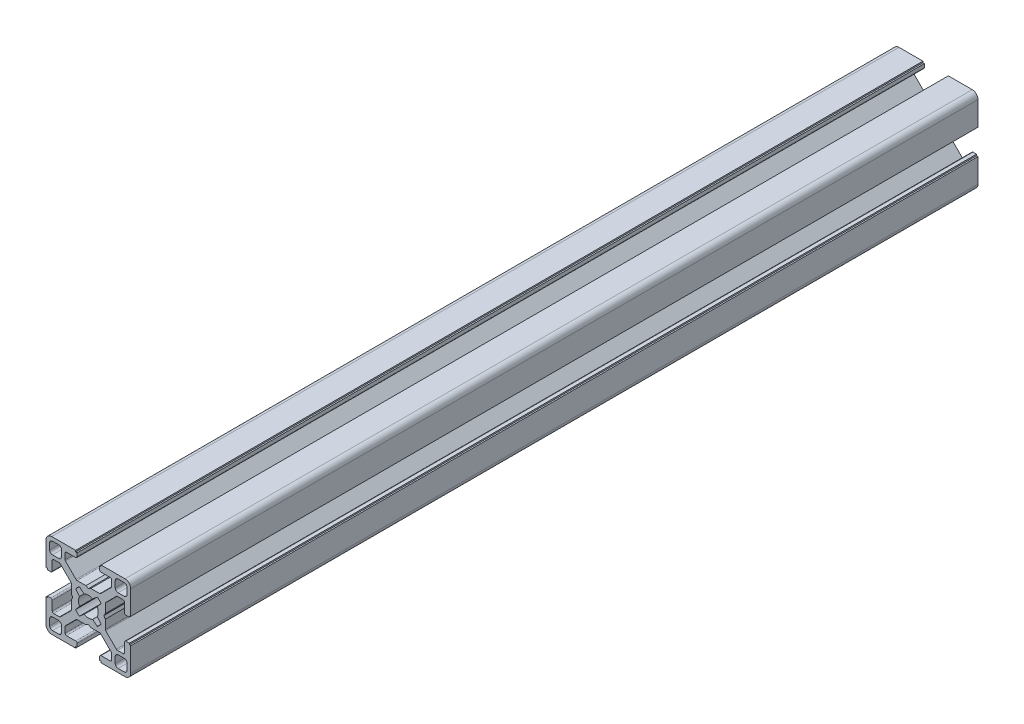
SolidWorks part; units mm, degrees
ref_plane "Front Plane" through (0, 0, 0) normal (0, 0, 1) x (1, 0, 0)
ref_plane "Top Plane" through (0, 0, 0) normal (0, 1, 0) x (1, 0, 0)
ref_plane "Right Plane" through (0, 0, 0) normal (1, 0, 0) x (0, 0, -1)
sketch "Sketch1" plane through (0, 0, 0) normal (0, 0, 1) x (1, 0, 0)
  line L0 (-15, 0) -> (15, 0) construction
  line L1 (0, -15) -> (0, 15) construction
  line L2 (-4.5, 15) -> (4.5, 15) construction
  line L3 (-4, -15) -> (4, -15) construction
  line L4 (-4.5, 15) -> (-4.5, 14.5)
  line L5 (-4.5, 14.5) -> (-4, 14.5)
  line L6 (-4, 14.5) -> (-4, 13.29)
  line L7 (-4.5, 12.79) -> (-7.7675, 12.79)
  line L8 (-8.2675, 12.29) -> (-8.2675, 10.2707)
  line L9 (-8.1211, 9.9171) -> (-4.3504, 6.1464)
  line L10 (-3.9968, 6) -> (0, 6)
  line L11 (0, 0) -> (-15, 15) construction
  line L12 (-4.5, 15) -> (-12.968, 15)
  line L14 (-12.705, 9.5135) -> (-10.5135, 9.5135)
  line L15 (-13.705, 10.5135) -> (-13.705, 12.705)
  line L16 (-12.705, 13.705) -> (-10.5135, 13.705)
  line L17 (-9.5135, 10.5135) -> (-9.5135, 12.705)
  line L18 (-13.705, 9.5135) -> (-9.5135, 13.705) construction
  line L19 (-13.705, 13.705) -> (-9.5135, 9.5135) construction
  line L20 (-3.1568, 4.5038) -> (-1.5303, 3.1477) construction
  line L21 (-4.5038, 3.1568) -> (-3.1477, 1.5303) construction
  line L22 (-6, 3.9968) -> (-6, 0)
  line L23 (-9.9171, 8.1211) -> (-6.1464, 4.3504)
  line L24 (-15, 4.5) -> (-15, 12.968)
  line L25 (-12.29, 8.2675) -> (-10.2707, 8.2675)
  line L26 (-12.79, 4.5) -> (-12.79, 7.7675)
  line L27 (-14.5, 4) -> (-13.29, 4)
  line L28 (-14.5, 4.5) -> (-14.5, 4)
  line L29 (-15, 4.5) -> (-14.5, 4.5)
  circle A0 centre (0, 0) radius 3.5
  arc A1 (-12.968, 15) -> (-15, 12.968) centre (-12.968, 12.968) ccw
  circle A2 centre (0, 0) radius 5.5 construction
  arc A3 (-10.5135, 9.5135) -> (-9.5135, 10.5135) centre (-10.5135, 10.5135) ccw
  arc A4 (-13.705, 12.705) -> (-12.705, 13.705) centre (-12.705, 12.705) cw
  arc A5 (-10.5135, 13.705) -> (-9.5135, 12.705) centre (-10.5135, 12.705) cw
  arc A6 (-12.705, 9.5135) -> (-13.705, 10.5135) centre (-12.705, 10.5135) cw
  arc A7 (-12.79, 4.5) -> (-13.29, 4) centre (-13.29, 4.5) cw
  arc A8 (-12.29, 8.2675) -> (-12.79, 7.7675) centre (-12.29, 7.7675) ccw
  arc A9 (-9.9171, 8.1211) -> (-10.2707, 8.2675) centre (-10.2707, 7.7675) ccw
  arc A10 (-6, 3.9968) -> (-6.1464, 4.3504) centre (-6.5, 3.9968) ccw
  arc A11 (-4.3504, 6.1464) -> (-3.9968, 6) centre (-3.9968, 6.5) ccw
  arc A12 (-4, 13.29) -> (-4.5, 12.79) centre (-4.5, 13.29) cw
  arc A13 (-7.7675, 12.79) -> (-8.2675, 12.29) centre (-7.7675, 12.29) ccw
  arc A14 (-8.2675, 10.2707) -> (-8.1211, 9.9171) centre (-7.7675, 10.2707) ccw
  point P4 (0, 0)
  point P8 (0, 0)
  point P13 (0, 15)
  point P15 (0, -15)
  point P16 (0, 6)
  point P23 (-11.6092, 11.6093)
  point P26 (0, 6)
  point P62 (-12.79, 4)
  point P65 (-12.79, 8.2675)
  point P68 (-10.0636, 8.2675)
  point P71 (-6, 4.2039)
  point P74 (-4.2039, 6)
  point P77 (-4, 12.79)
  point P80 (-8.2675, 12.79)
  point P83 (-8.2675, 10.0636)
  dimension "Center Hole Diameter" = 7
  dimension "D11" = 2.032
  dimension "D9" = 11
  dimension "D13" = 1
  dimension "D14" = 0.5
  dimension "Rail Height" = 30
  dimension "Rail Width" = 30
  dimension "T-Slot Width" = 8
  dimension "T-Slot Depth" = 9
  dimension "D1" = 9
  dimension "D2" = 45
  dimension "D3" = 8
  dimension "D4" = 2.21
  dimension "D5" = 16.535
  dimension "D7" = 2.54
  dimension "D6" = 1.295
  dimension "D8" = 1.246
  dimension "D10" = 10.36
  dimension "D12" = 1.905
sketch "Sketch2" plane through (0, 0, 0) normal (1, 0, 0) x (0, 0, -1)
  line L0 (-76.2, 0) -> (76.2, 0) construction
  line L2 (0, -15) -> (0, 15) construction
  line L3 (0, -15) -> (0, 15) construction
  line L4 (-76.2, -15) -> (-76.2, 15) construction
  line L5 (76.2, -15) -> (76.2, 15) construction
  point P0 (-38.7, 0)
  point P3 (0, 0)
  point P4 (38.7, 0)
  point P12 (-76.2, 0)
  point P14 (76.2, 0)
  dimension "Length" = 152.4
  dimension "D1" = 37.5
sketch "Sketch3" plane through (0, 0, 0) normal (0, 0, 1) x (1, 0, 0)
  line L0 (-4.5038, 3.1568) -> (-3.1477, 1.5303)
  line L1 (0, 3.5) -> (0, 5.5)
  line L2 (-5.5, 0) -> (-3.5, 0)
  line L7 (-6, 3.9968) -> (-6, 0) construction
  line L31 (-9.9171, 8.1211) -> (-6.1464, 4.3504) construction
  line L117 (-12.29, 8.2675) -> (-10.2707, 8.2675) construction
  line L118 (-12.79, 4.5) -> (-12.79, 7.7675) construction
  line L157 (-12.705, 9.5135) -> (-10.5135, 9.5135)
  line L158 (-9.5135, 10.5135) -> (-9.5135, 12.705)
  line L163 (-10.5135, 13.705) -> (-12.705, 13.705)
  line L164 (-13.705, 12.705) -> (-13.705, 10.5135)
  line L165 (-12.705, 9.5135) -> (-10.5135, 9.5135)
  line L166 (-9.5135, 10.5135) -> (-9.5135, 12.705)
  line L167 (-10.5135, 13.705) -> (-12.705, 13.705)
  line L168 (-13.705, 12.705) -> (-13.705, 10.5135)
  line L169 (-14.5, 4) -> (-13.29, 4) construction
  line L170 (-14.5, 4.5) -> (-14.5, 4) construction
  line L171 (-15, 4.5) -> (-14.5, 4.5) construction
  line L172 (-15, 4.5) -> (-15, 12.968) construction
  line L173 (-4.5, 15) -> (-12.968, 15) construction
  line L174 (-4.5, 15) -> (-4.5, 14.5) construction
  line L175 (-4.5, 14.5) -> (-4, 14.5) construction
  line L176 (-4, 14.5) -> (-4, 13.29) construction
  line L177 (-4.5, 12.79) -> (-7.7675, 12.79) construction
  line L178 (-8.2675, 12.29) -> (-8.2675, 10.2707) construction
  line L179 (-8.1211, 9.9171) -> (-4.3504, 6.1464) construction
  line L180 (-3.9968, 6) -> (0, 6) construction
  line L181 (-6, 3.9968) -> (-6, 0.866)
  line L182 (-9.9171, 8.1211) -> (-6.1464, 4.3504)
  line L183 (-12.29, 8.2675) -> (-10.2707, 8.2675)
  line L184 (-12.79, 4.5) -> (-12.79, 7.7675)
  line L185 (-14.5, 4) -> (-13.29, 4)
  line L186 (-14.5, 4.5) -> (-14.5, 4)
  line L187 (-15, 4.5) -> (-14.5, 4.5)
  line L188 (-15, 4.5) -> (-15, 12.968)
  line L189 (-4.5, 15) -> (-12.968, 15)
  line L190 (-4.5, 15) -> (-4.5, 14.5)
  line L191 (-4.5, 14.5) -> (-4, 14.5)
  line L192 (-4, 14.5) -> (-4, 13.29)
  line L193 (-4.5, 12.79) -> (-7.7675, 12.79)
  line L194 (-8.2675, 12.29) -> (-8.2675, 10.2707)
  line L195 (-8.1211, 9.9171) -> (-4.3504, 6.1464)
  line L196 (-3.9968, 6) -> (-0.866, 6)
  line L197 (-0.866, 6) -> (0, 5.5)
  line L198 (0, -15) -> (0, 15) construction
  line L199 (0, 0) -> (-15, 15) construction
  line L200 (0, 0) -> (-15, 15) construction
  line L201 (-3.1568, 4.5038) -> (-1.5303, 3.1477) construction
  line L202 (-3.1568, 4.5038) -> (-1.5303, 3.1477)
  line L203 (-6, 0.866) -> (-5.5, 0)
  line L204 (-15, 0) -> (15, 0) construction
  line L205 (-15, 0) -> (15, 0) construction
  line L206 (0, -15) -> (0, 15) construction
  arc A0 (-3.5, 0) -> (-3.1477, 1.5303) centre (0, 0) cw
  arc A10 (-6, 3.9968) -> (-6.1464, 4.3504) centre (-6.5, 3.9968) ccw construction
  circle A16 centre (0, 0) radius 3.5
  arc A18 (0, 3.5) -> (-1.5303, 3.1477) centre (0, 0) ccw
  arc A20 (-9.9171, 8.1211) -> (-10.2707, 8.2675) centre (-10.2707, 7.7675) ccw construction
  arc A22 (-12.29, 8.2675) -> (-12.79, 7.7675) centre (-12.29, 7.7675) ccw construction
  arc A28 (-13.29, 4) -> (-12.79, 4.5) centre (-13.29, 4.5) ccw construction
  arc A29 (-10.5135, 9.5135) -> (-9.5135, 10.5135) centre (-10.5135, 10.5135) ccw
  arc A30 (-9.5135, 12.705) -> (-10.5135, 13.705) centre (-10.5135, 12.705) ccw
  arc A31 (-12.705, 13.705) -> (-13.705, 12.705) centre (-12.705, 12.705) ccw
  arc A32 (-13.705, 10.5135) -> (-12.705, 9.5135) centre (-12.705, 10.5135) ccw
  arc A33 (-10.5135, 9.5135) -> (-9.5135, 10.5135) centre (-10.5135, 10.5135) ccw
  arc A34 (-9.5135, 12.705) -> (-10.5135, 13.705) centre (-10.5135, 12.705) ccw
  arc A35 (-12.705, 13.705) -> (-13.705, 12.705) centre (-12.705, 12.705) ccw
  arc A36 (-13.705, 10.5135) -> (-12.705, 9.5135) centre (-12.705, 10.5135) ccw
  arc A37 (-12.968, 15) -> (-15, 12.968) centre (-12.968, 12.968) ccw construction
  arc A38 (-4.5, 12.79) -> (-4, 13.29) centre (-4.5, 13.29) ccw construction
  arc A39 (-7.7675, 12.79) -> (-8.2675, 12.29) centre (-7.7675, 12.29) ccw construction
  arc A40 (-8.2675, 10.2707) -> (-8.1211, 9.9171) centre (-7.7675, 10.2707) ccw construction
  arc A41 (-4.3504, 6.1464) -> (-3.9968, 6) centre (-3.9968, 6.5) ccw construction
  arc A42 (-6, 3.9968) -> (-6.1464, 4.3504) centre (-6.5, 3.9968) ccw
  arc A43 (-9.9171, 8.1211) -> (-10.2707, 8.2675) centre (-10.2707, 7.7675) ccw
  arc A44 (-12.29, 8.2675) -> (-12.79, 7.7675) centre (-12.29, 7.7675) ccw
  arc A45 (-13.29, 4) -> (-12.79, 4.5) centre (-13.29, 4.5) ccw
  arc A46 (-12.968, 15) -> (-15, 12.968) centre (-12.968, 12.968) ccw
  arc A47 (-4.5, 12.79) -> (-4, 13.29) centre (-4.5, 13.29) ccw
  arc A48 (-7.7675, 12.79) -> (-8.2675, 12.29) centre (-7.7675, 12.29) ccw
  arc A49 (-8.2675, 10.2707) -> (-8.1211, 9.9171) centre (-7.7675, 10.2707) ccw
  arc A50 (-4.3504, 6.1464) -> (-3.9968, 6) centre (-3.9968, 6.5) ccw
  circle A51 centre (0, 0) radius 5.5 construction
  arc A52 (-3.1568, 4.5038) -> (-4.5038, 3.1568) centre (0, 0) ccw
  dimension "D3" = 60
  dimension "D4" = 60
  dimension "D1" = 0
  dimension "D2" = 0
extrude "Boss-Extrude1" add sketch "Sketch3" along normal mid plane 300
pattern_circular "CirPattern1" count 4 over 360 about axis through (0, 0, 76.2) along (0, 0, -1) of "Boss-Extrude1"
ref_plane "Contact Plane1" through (15, 0, 0) normal (1, 0, 0) x (0, 0, -1)
ref_plane "Contact Plane2" through (0, -15, 0) normal (0, 1, 0) x (1, 0, 0)
ref_plane "Contact Plane3" through (-15, 0, 0) normal (1, 0, 0) x (0, 0, -1)
ref_plane "Contact Plane4" through (0, 15, 0) normal (0, 1, 0) x (1, 0, 0)
equation "\"D1@Sketch2\" = \"Rail Height@Sketch1\" * 1.25"
equation "\"D1@Sketch1\"=\"T-Slot Width@Sketch1\"+1mm"
equation "\"D3@Sketch1\"=\"T-Slot Width@Sketch1\""
equation "\"D1@Boss-Extrude1\"=\"Width\""
equation "\"Width\"= 300mm"
